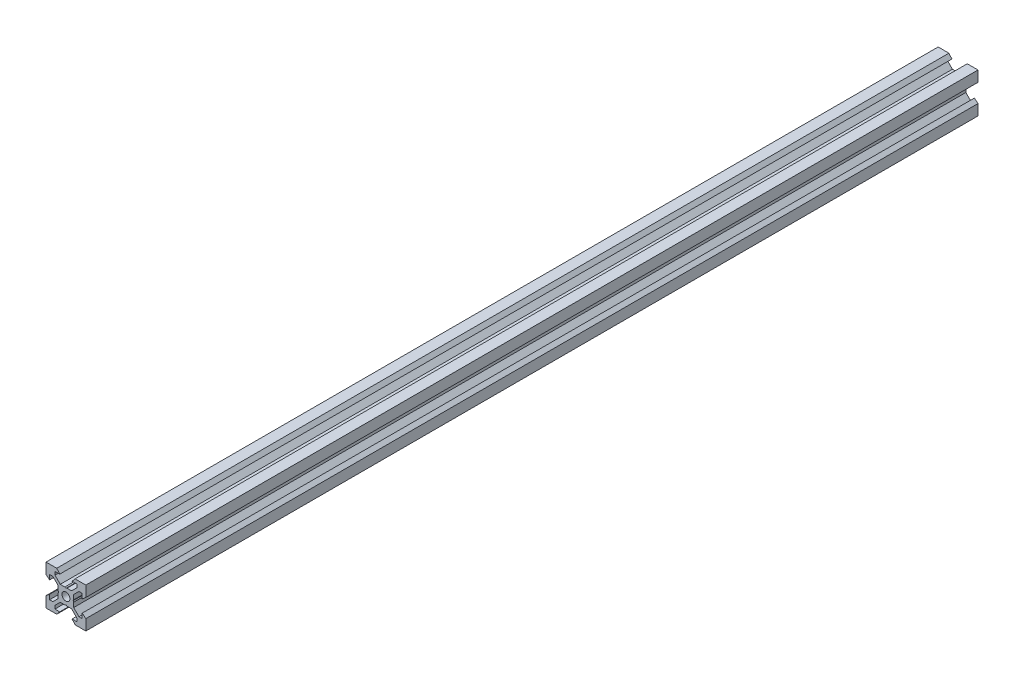
SolidWorks part; units mm, degrees
ref_plane "Front Plane" through (0, 0, 0) normal (0, 0, 1) x (1, 0, 0)
ref_plane "Top Plane" through (0, 0, 0) normal (0, 1, 0) x (1, 0, 0)
ref_plane "Right Plane" through (0, 0, 0) normal (1, 0, 0) x (0, 0, -1)
sketch "Sketch1" plane through (0, 0, 0) normal (0, 0, 1) x (1, 0, 0)
  line L0 (10, 10) -> (4.6104, 10) construction
  line L1 (10, 10) -> (10, 4.6104) construction
  line L2 (10, -10) -> (10, -4.6104) construction
  line L3 (10, -10) -> (4.6104, -10) construction
  line L4 (10, 10) -> (10, 4.6104)
  line L5 (6.5607, 5.5) -> (8.2, 5.5)
  line L6 (5.5, 8.2) -> (5.5, 6.5607)
  line L7 (10, 10) -> (4.6104, 10)
  line L8 (10, 10) -> (10, 4.6104)
  line L9 (6.5607, 5.5) -> (3.9, 2.8393)
  line L10 (5.5, 6.5607) -> (2.8393, 3.9)
  line L11 (10, 4.6104) -> (8.2, 3.1)
  line L12 (4.6104, 10) -> (3.1, 8.2)
  line L13 (8.2, 3.1) -> (8.2, 5.5)
  line L14 (3.1, 8.2) -> (5.5, 8.2)
  line L15 (-6.5607, 5.5) -> (-8.2, 5.5)
  line L16 (6.5607, -5.5) -> (8.2, -5.5)
  line L17 (3.1, -8.2) -> (5.5, -8.2)
  line L18 (8.2, -3.1) -> (8.2, -5.5)
  line L19 (4.6104, -10) -> (3.1, -8.2)
  line L20 (10, -4.6104) -> (8.2, -3.1)
  line L21 (0.5196, -3.9) -> (0, -3.6)
  line L22 (0.5196, 3.9) -> (0, 3.6)
  line L23 (3.6, 0) -> (3.9, -0.5196)
  line L24 (3.9, 0.5196) -> (3.6, 0)
  line L25 (3.9, 0.5196) -> (3.9, 2.8393)
  line L26 (2.8393, 3.9) -> (0.5196, 3.9)
  line L27 (3.9, -2.8393) -> (3.9, -0.5196)
  line L28 (2.8393, -3.9) -> (0.5196, -3.9)
  line L29 (5.5, -6.5607) -> (2.8393, -3.9)
  line L30 (6.5607, -5.5) -> (3.9, -2.8393)
  line L31 (10, -10) -> (10, -4.6104)
  line L32 (10, -10) -> (4.6104, -10)
  line L33 (5.5, -8.2) -> (5.5, -6.5607)
  line L34 (-6.5607, -5.5) -> (-8.2, -5.5)
  line L35 (10, -10) -> (10, -4.6104)
  line L36 (0, 0) -> (0, 8.2) construction
  line L37 (-10, -10) -> (-4.6104, -10) construction
  line L38 (-10, -10) -> (-10, -4.6104) construction
  line L39 (-10, 10) -> (-10, 4.6104) construction
  line L40 (-10, 10) -> (-4.6104, 10) construction
  line L41 (-10, -10) -> (-10, -4.6104)
  line L43 (-5.5, -8.2) -> (-5.5, -6.5607)
  line L44 (-10, -10) -> (-4.6104, -10)
  line L45 (-10, -10) -> (-10, -4.6104)
  line L46 (-6.5607, -5.5) -> (-3.9, -2.8393)
  line L47 (-5.5, -6.5607) -> (-2.8393, -3.9)
  line L48 (-2.8393, -3.9) -> (-0.5196, -3.9)
  line L49 (-3.9, -2.8393) -> (-3.9, -0.5196)
  line L50 (-2.8393, 3.9) -> (-0.5196, 3.9)
  line L51 (-3.9, 0.5196) -> (-3.9, 2.8393)
  line L52 (-3.9, 0.5196) -> (-3.6, 0)
  line L53 (-3.6, 0) -> (-3.9, -0.5196)
  line L54 (-0.5196, 3.9) -> (0, 3.6)
  line L55 (-0.5196, -3.9) -> (0, -3.6)
  line L56 (-10, -4.6104) -> (-8.2, -3.1)
  line L57 (-4.6104, -10) -> (-3.1, -8.2)
  line L58 (-8.2, -3.1) -> (-8.2, -5.5)
  line L59 (-3.1, -8.2) -> (-5.5, -8.2)
  line L60 (-10, -10) -> (10, -10) construction
  line L61 (-10, -10) -> (-10, 10) construction
  line L62 (-3.1, 8.2) -> (-5.5, 8.2)
  line L63 (-8.2, 3.1) -> (-8.2, 5.5)
  line L64 (-4.6104, 10) -> (-3.1, 8.2)
  line L65 (-10, 4.6104) -> (-8.2, 3.1)
  line L66 (-5.5, 6.5607) -> (-2.8393, 3.9)
  line L67 (-6.5607, 5.5) -> (-3.9, 2.8393)
  line L68 (-10, 10) -> (-10, 4.6104)
  line L69 (-10, 10) -> (-4.6104, 10)
  line L70 (-5.5, 8.2) -> (-5.5, 6.5607)
  line L71 (-10, 10) -> (10, 10) construction
  line L72 (-10, 10) -> (-10, 4.6104)
  line L73 (10, -10) -> (10, 10) construction
  line L74 (-10, -10) -> (10, 10) construction
  line L75 (-10, 10) -> (10, -10) construction
  circle A0 centre (0, 0) radius 2
  dimension "D7" = 4
  dimension "D1" = 20
  dimension "D2" = 5.3896
  dimension "D3" = 4.5
  dimension "D4" = 50
  dimension "D5" = 1.8
  dimension "D6" = 1.5104
  dimension "D8" = 5.5
  dimension "D9" = 120
  dimension "D10" = 0.3
  dimension "D11" = 2.3197
  dimension "D12" = 7.8
  dimension "D13" = 7.8
  dimension "D14" = 1.5
  dimension "D15" = 2.6607
extrude "Boss-Extrude1" add sketch "Sketch1" along normal mid plane 448 contours L70 L62 L64 L69 L68 L65 L63 L15 L67 L51 L52 L53 L49 L46 L34 L58 L56 L41 L44 L57 L59 L43 L47 L48 L55 L21 L28 L29 L33 L17 L19 L32 L31 L20 L18 L16 L30 L27 L23 L24 L25 L9 L5 L13 L11 L4 L7 L12 L14 L6 L10 region at (9.7172, 7.3052, 0)
